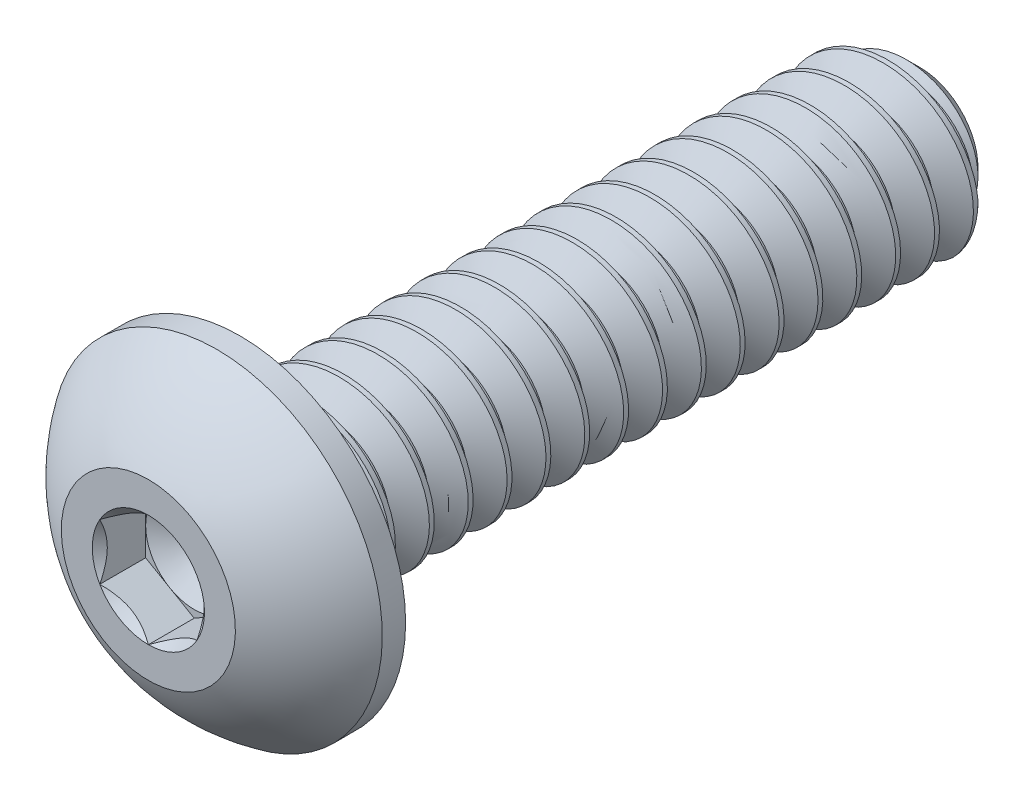
SolidWorks part; units mm, degrees
ref_plane "Front" through (0, 0, 0) normal (0, 0, 1) x (1, 0, 0)
ref_plane "Top" through (0, 0, 0) normal (0, 1, 0) x (1, 0, 0)
ref_plane "Right" through (0, 0, 0) normal (1, 0, 0) x (0, 0, -1)
sketch "Sketch1" plane through (0, 0, 0) normal (1, 0, 0) x (0, 0, -1)
  line L0 (0, 0) -> (-1.4986, 0) construction
  line L1 (0, 0) -> (11.1125, 0)
  line L2 (0, 0) -> (0, 1.4224)
  line L3 (0, 1.4224) -> (11.1125, 1.4224)
  line L4 (11.1125, 0) -> (11.1125, 1.4224)
  line L5 (0, -1.4224) -> (11.1125, -1.4224) construction
  dimension "D1" = 11.1125
  dimension "Thread Dia" = 2.8448
  dimension "Length" = 11.1125
  dimension "Head Height" = 1.4986
revolve "Revolve1" add sketch "Sketch1" angle 360 about L0
ref_plane "Plane1" through (0, 0, 1.4986) normal (0, 0, 1) x (1, 0, 0)
chamfer "Chamfer1" distance 0.4763 angle 45 1 edges at (0, 1.4224, -11.1125)
sketch "Sketch10" plane through (0, 0, 0) normal (1, 0, 0) x (0, 0, -1)
  line L0 (11.1125, 1.4224) -> (11.6681, 1.4224)
  line L1 (11.6681, 1.4224) -> (11.43, 1.01)
  line L2 (11.43, 1.01) -> (11.3506, 1.01)
  line L3 (11.3506, 1.01) -> (11.1125, 1.4224)
  line L4 (11.2316, 1.2162) -> (11.5491, 1.2162) construction
  dimension "D1" = 60
  dimension "D2" = 0.0794
  dimension "D3" = 0.3175
sketch "Sketch11" plane through (0, 0, -11.1125) normal (0, 0, -1) x (-1, 0, 0)
  circle A1 centre (0, 0) radius 0.9462
  circle A2 centre (0, 0) radius 0.9462
  dimension "D1" = 0
curve "Helix/Spiral1" pitch 0.635 height 14.2875 turns 22.5
sweep "Cut-Sweep1" cut profiles "Sketch10" path "Helix/Spiral1"
sketch "Sketch4" plane through (0, 0, 0) normal (0, 0, 1) x (1, 0, 0)
  circle A0 centre (0, 0) radius 2.7051
  dimension "Head Dia" = 5.4102
extrude "Extrude1" add sketch "Sketch4" along normal up to surface (1.4986 mm away) up to plane "Plane1"
sketch "Sketch9" plane through (0, 0, 0) normal (1, 0, 0) x (0, 0, -1)
  line L0 (0, 2.7051) -> (-0.381, 2.7051)
  line L1 (0, 2.7051) -> (0, 3.0861)
  line L2 (0, 3.0861) -> (-1.8796, 3.0861)
  line L3 (0, 0) -> (-1.4986, 0) construction
  line L4 (-1.8796, 3.0861) -> (-1.8796, 1.4224)
  line L5 (-1.8796, 1.4224) -> (-1.4986, 1.4224)
  line L6 (0, 0) -> (0, 1.4224) construction
  line L10 (0, 2.7051) -> (-1.4986, 2.7051) construction
  line L11 (0, 1.4224) -> (11.1125, 1.4224) construction
  line L12 (-1.4986, 2.7051) -> (-1.4986, -2.7051) construction
  arc A0 (-1.4986, 1.4224) -> (-0.381, 2.7051) centre (1.4288, 0) cw
  dimension "Side Head Height" = 0.381
revolve "Cut-Revolve3" cut sketch "Sketch9" angle 360 about L3
sketch "Sketch6" plane through (0, 0, 1.4986) normal (0, 0, 1) x (1, 0, 0)
  line L1 (0, -0.9165) -> (0.7937, -0.4583)
  line L2 (0.7937, -0.4583) -> (0.7937, 0.4583)
  line L3 (0.7937, 0.4583) -> (0, 0.9165)
  line L4 (0, 0.9165) -> (-0.7938, 0.4583)
  line L5 (-0.7938, 0.4583) -> (-0.7938, -0.4583)
  line L6 (-0.7938, -0.4583) -> (0, -0.9165)
  circle A0 centre (0, 0) radius 0.7938 construction
  dimension "Hex" = 1.5875
extrude "Cut-Extrude1" cut sketch "Sketch6" against normal blind 0.7493
sketch "Sketch7" plane through (0, 0, 1.4986) normal (0, 0, 1) x (1, 0, 0)
  circle A0 centre (0, 0) radius 0.9165
extrude "Cut-Extrude4" cut sketch "Sketch7" against normal blind 0.7493 draft 45
sketch "Sketch8" plane through (0, 0, 0.7493) normal (0, 0, 1) x (1, 0, 0)
  circle A0 centre (0, 0) radius 0.7938 construction
  circle A1 centre (0, 0) radius 0.7938
extrude "Cut-Extrude5" cut sketch "Sketch8" against normal blind 0.2498 draft 60
sketch "Sketch12" plane through (0, 0, 0) normal (1, 0, 0) x (0, 0, -1)
  line L1 (0, -1.4224) -> (11.1125, -1.4224) construction
  spline S2 degree 2 poles (10.6363, 0.013) (10.5944, 0.5945) (10.5569, 1.0058) (10.504, 1.5865) (10.451, 1.3739) (10.3981, 1.1614) (10.3452, 0.3681) (10.2923, -0.4251) (10.2394, -1.0058) (10.1865, -1.5865) (10.1335, -1.3739) (10.0806, -1.1614) (10.0277, -0.3681) (9.9748, 0.4251) (9.9219, 1.0058) (9.869, 1.5865) (9.816, 1.3739) (9.7631, 1.1614) (9.7102, 0.3681) (9.6573, -0.4251) (9.6044, -1.0058) (9.5515, -1.5865) (9.4985, -1.3739) (9.4456, -1.1614) (9.3927, -0.3681) (9.3398, 0.4251) (9.2869, 1.0058) (9.234, 1.5865) (9.181, 1.3739) (9.1281, 1.1614) (9.0752, 0.3681) (9.0223, -0.4251) (8.9694, -1.0058) (8.9165, -1.5865) (8.8635, -1.3739) (8.8106, -1.1614) (8.7577, -0.3681) (8.7048, 0.4251) (8.6519, 1.0058) (8.599, 1.5865) (8.546, 1.3739) (8.4931, 1.1614) (8.4402, 0.3681) (8.3873, -0.4251) (8.3344, -1.0058) (8.2815, -1.5865) (8.2285, -1.3739) (8.1756, -1.1614) (8.1227, -0.3681) (8.0698, 0.4251) (8.0169, 1.0058) (7.964, 1.5865) (7.911, 1.3739) (7.8581, 1.1614) (7.8052, 0.3681) (7.7523, -0.4251) (7.6994, -1.0058) (7.6465, -1.5865) (7.5935, -1.3739) (7.5406, -1.1614) (7.4877, -0.3681) (7.4348, 0.4251) (7.3819, 1.0058) (7.329, 1.5865) (7.276, 1.3739) (7.2231, 1.1614) (7.1702, 0.3681) (7.1173, -0.4251) (7.0644, -1.0058) (7.0115, -1.5865) (6.9585, -1.3739) (6.9056, -1.1614) (6.8527, -0.3681) (6.7998, 0.4251) (6.7469, 1.0058) (6.694, 1.5865) (6.641, 1.3739) (6.5881, 1.1614) (6.5352, 0.3681) (6.4823, -0.4251) (6.4294, -1.0058) (6.3765, -1.5865) (6.3235, -1.3739) (6.2706, -1.1614) (6.2177, -0.3681) (6.1648, 0.4251) (6.1119, 1.0058) (6.059, 1.5865) (6.006, 1.3739) (5.9531, 1.1614) (5.9002, 0.3681) (5.8473, -0.4251) (5.7944, -1.0058) (5.7415, -1.5865) (5.6885, -1.3739) (5.6356, -1.1614) (5.5827, -0.3681) (5.5298, 0.4251) (5.4769, 1.0058) (5.424, 1.5865) (5.371, 1.3739) (5.3181, 1.1614) (5.2652, 0.3681) (5.2123, -0.4251) (5.1594, -1.0058) (5.1065, -1.5865) (5.0535, -1.3739) (5.0006, -1.1614) (4.9477, -0.3681) (4.8948, 0.4251) (4.8419, 1.0058) (4.789, 1.5865) (4.736, 1.3739) (4.6831, 1.1614) (4.6302, 0.3681) (4.5773, -0.4251) (4.5244, -1.0058) (4.4715, -1.5865) (4.4185, -1.3739) (4.3656, -1.1614) (4.3127, -0.3681) (4.2598, 0.4251) (4.2069, 1.0058) (4.154, 1.5865) (4.101, 1.3739) (4.0481, 1.1614) (3.9952, 0.3681) (3.9423, -0.4251) (3.8894, -1.0058) (3.8365, -1.5865) (3.7835, -1.3739) (3.7306, -1.1614) (3.6777, -0.3681) (3.6248, 0.4251) (3.5719, 1.0058) (3.519, 1.5865) (3.466, 1.3739) (3.4131, 1.1614) (3.3602, 0.3681) (3.3073, -0.4251) (3.2544, -1.0058) (3.2015, -1.5865) (3.1485, -1.3739) (3.0956, -1.1614) (3.0427, -0.3681) (2.9898, 0.4251) (2.9369, 1.0058) (2.884, 1.5865) (2.831, 1.3739) (2.7781, 1.1614) (2.7252, 0.3681) (2.6723, -0.4251) (2.6194, -1.0058) (2.5665, -1.5865) (2.5135, -1.3739) (2.4606, -1.1614) (2.4077, -0.3681) (2.3548, 0.4251) (2.3019, 1.0058) (2.249, 1.5865) (2.196, 1.3739) (2.1431, 1.1614) (2.0902, 0.3681) (2.0373, -0.4251) (1.9844, -1.0058) (1.9315, -1.5865) (1.8785, -1.3739) (1.8256, -1.1614) (1.7727, -0.3681) (1.7198, 0.4251) (1.6669, 1.0058) (1.614, 1.5865) (1.561, 1.3739) (1.5081, 1.1614) (1.4552, 0.3681) (1.4023, -0.4251) (1.3494, -1.0058) (1.2965, -1.5865) (1.2435, -1.3739) (1.1906, -1.1614) (1.1377, -0.3681) (1.0848, 0.4251) (1.0319, 1.0058) (0.979, 1.5865) (0.926, 1.3739) (0.8731, 1.1614) (0.8202, 0.3681) (0.7673, -0.4251) (0.7144, -1.0058) (0.6615, -1.5865) (0.6085, -1.3739) (0.5556, -1.1614) (0.5027, -0.3681) (0.4498, 0.4251) (0.3969, 1.0058) (0.344, 1.5865) (0.291, 1.3739) (0.2381, 1.1614) (0.1852, 0.3681) (0.1323, -0.4251) (0.0794, -1.0058) (0.0419, -1.417) (0, -1.4223) knots 0.038138 0.038138 0.038138 0.043478 0.043478 0.050725 0.050725 0.057971 0.057971 0.065217 0.065217 0.072464 0.072464 0.07971 0.07971 0.086957 0.086957 0.094203 0.094203 0.101449 0.101449 0.108696 0.108696 0.115942 0.115942 0.123188 0.123188 0.130435 0.130435 0.137681 0.137681 0.144928 0.144928 0.152174 0.152174 0.15942 0.15942 0.166667 0.166667 0.173913 0.173913 0.181159 0.181159 0.188406 0.188406 0.195652 0.195652 0.202899 0.202899 0.210145 0.210145 0.217391 0.217391 0.224638 0.224638 0.231884 0.231884 0.23913 0.23913 0.246377 0.246377 0.253623 0.253623 0.26087 0.26087 0.268116 0.268116 0.275362 0.275362 0.282609 0.282609 0.289855 0.289855 0.297101 0.297101 0.304348 0.304348 0.311594 0.311594 0.318841 0.318841 0.326087 0.326087 0.333333 0.333333 0.34058 0.34058 0.347826 0.347826 0.355072 0.355072 0.362319 0.362319 0.369565 0.369565 0.376812 0.376812 0.384058 0.384058 0.391304 0.391304 0.398551 0.398551 0.405797 0.405797 0.413043 0.413043 0.42029 0.42029 0.427536 0.427536 0.434783 0.434783 0.442029 0.442029 0.449275 0.449275 0.456522 0.456522 0.463768 0.463768 0.471014 0.471014 0.478261 0.478261 0.485507 0.485507 0.492754 0.492754 0.5 0.5 0.507246 0.507246 0.514493 0.514493 0.521739 0.521739 0.528986 0.528986 0.536232 0.536232 0.543478 0.543478 0.550725 0.550725 0.557971 0.557971 0.565217 0.565217 0.572464 0.572464 0.57971 0.57971 0.586957 0.586957 0.594203 0.594203 0.601449 0.601449 0.608696 0.608696 0.615942 0.615942 0.623188 0.623188 0.630435 0.630435 0.637681 0.637681 0.644928 0.644928 0.652174 0.652174 0.65942 0.65942 0.666667 0.666667 0.673913 0.673913 0.681159 0.681159 0.688406 0.688406 0.695652 0.695652 0.702899 0.702899 0.710145 0.710145 0.717391 0.717391 0.724638 0.724638 0.731884 0.731884 0.73913 0.73913 0.746377 0.746377 0.753623 0.753623 0.76087 0.76087 0.76621 0.76621 0.76621 weights 0.948065 0.901259 1 0.866025 1 0.866025 1 0.866025 1 0.866025 1 0.866025 1 0.866025 1 0.866025 1 0.866025 1 0.866025 1 0.866025 1 0.866025 1 0.866025 1 0.866025 1 0.866025 1 0.866025 1 0.866025 1 0.866025 1 0.866025 1 0.866025 1 0.866025 1 0.866025 1 0.866025 1 0.866025 1 0.866025 1 0.866025 1 0.866025 1 0.866025 1 0.866025 1 0.866025 1 0.866025 1 0.866025 1 0.866025 1 0.866025 1 0.866025 1 0.866025 1 0.866025 1 0.866025 1 0.866025 1 0.866025 1 0.866025 1 0.866025 1 0.866025 1 0.866025 1 0.866025 1 0.866025 1 0.866025 1 0.866025 1 0.866025 1 0.866025 1 0.866025 1 0.866025 1 0.866025 1 0.866025 1 0.866025 1 0.866025 1 0.866025 1 0.866025 1 0.866025 1 0.866025 1 0.866025 1 0.866025 1 0.866025 1 0.866025 1 0.866025 1 0.866025 1 0.866025 1 0.866025 1 0.866025 1 0.866025 1 0.866025 1 0.866025 1 0.866025 1 0.866025 1 0.866025 1 0.866025 1 0.866025 1 0.866025 1 0.866025 1 0.866025 1 0.866025 1 0.866025 1 0.866025 1 0.866025 1 0.866025 1 0.866025 1 0.866025 1 0.866025 1 0.866025 1 0.866025 1 0.866025 1 0.866025 1 0.866025 1 0.866025 1 0.866025 1 0.866025 1 0.866025 1 0.866025 1 0.866025 1 0.866025 1 0.901259 0.948065 construction
  point P0 (10.1591, -1.4224)
equation "\"D1@Cut-Extrude1\"=\"Head Height@Sketch1\"/2"
equation "\"D1@Cut-Extrude4\"=\"D1@Cut-Extrude1\""
equation "\"D1@Cut-Extrude5\"=\"D1@Cut-Extrude1\"/3"
equation "\"D3@Helix/Spiral1\" = \"Length@Sketch1\" + .125"
equation "\"D1@Chamfer1\" = \"D4@Helix/Spiral1\" * .75"
equation "\"D2@Sketch10\" = \"D4@Helix/Spiral1\" * .125"
equation "\"D3@Sketch10\" = \"D4@Helix/Spiral1\" * .5"
